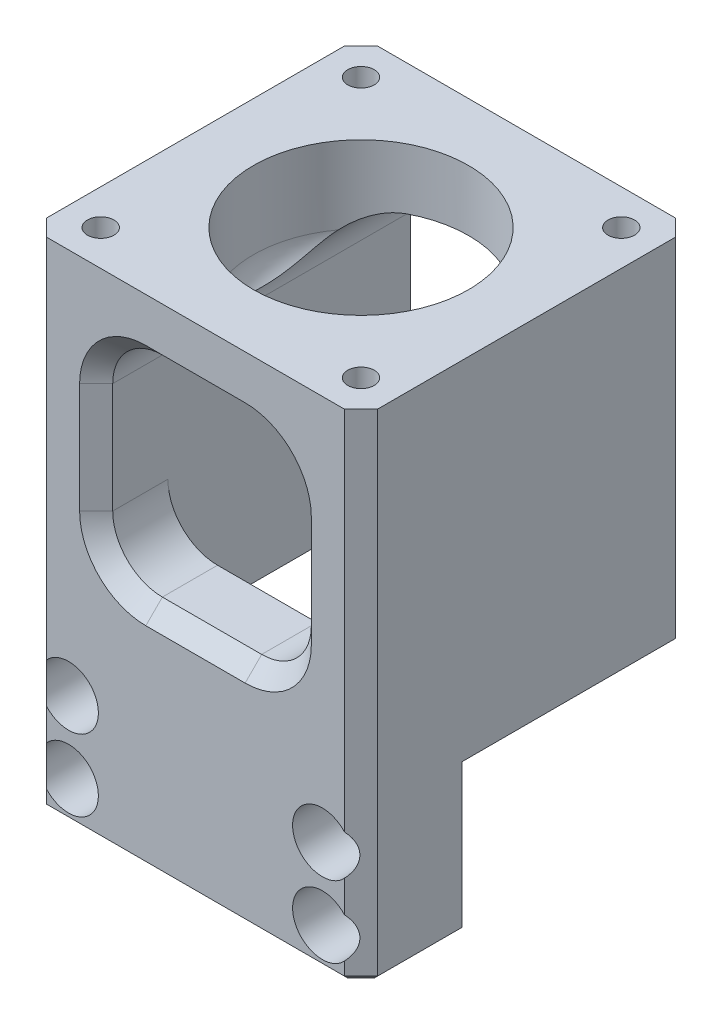
SolidWorks part; units mm, degrees
ref_plane "Front Plane" through (0, 0, 0) normal (0, 0, 1) x (1, 0, 0)
ref_plane "Top Plane" through (0, 0, 0) normal (0, 1, 0) x (1, 0, 0)
ref_plane "Right Plane" through (0, 0, 0) normal (1, 0, 0) x (0, 0, -1)
sketch "Sketch1" plane through (0, 0, 0) normal (0, 1, 0) x (1, 0, 0)
  line L1 (30, -30) -> (-30, -30)
  line L2 (30, -30) -> (30, 30)
  line L3 (30, 30) -> (-30, 30)
  line L4 (-30, -30) -> (-30, 30)
  line L5 (30, -30) -> (-30, 30) construction
  line L6 (30, 30) -> (-30, -30) construction
  point P0 (0, 0)
  dimension "D1" = 60
extrude "Boss-Extrude1" add sketch "Sketch1" along normal blind 90
sketch "Sketch2" plane through (0, 0, 0) normal (1, 0, 0) x (0, 0, -1)
  line L1 (30, 0) -> (-10.7, 0)
  line L2 (30, 0) -> (30, 26)
  line L3 (30, 26) -> (-10.7, 26)
  line L4 (-10.7, 0) -> (-10.7, 26)
  line L6 (-30, 90) -> (-30, 0) construction
  dimension "D1" = 19.3
  dimension "D2" = 26
extrude "Cut-Extrude1" cut sketch "Sketch2" against normal through all both and the other way through all
sketch "Sketch4" plane through (0, 0, -30) normal (0, 0, -1) x (-1, 0, 0)
  line L4 (0, 60.4882) -> (0, 24.8111) construction
  line L5 (-30, 90) -> (-30, 26) construction
  line L6 (18, 41) -> (-18, 41)
  line L7 (18, 41) -> (18, 79)
  line L8 (18, 79) -> (-18, 79)
  line L9 (-18, 41) -> (-18, 79)
  line L10 (18, 41) -> (-18, 79) construction
  line L11 (18, 79) -> (-18, 41) construction
  line L12 (-30, 90) -> (30, 90) construction
  line L13 (30, 26) -> (-30, 26) construction
  point P1 (0, 60)
  dimension "D1" = 12
  dimension "D2" = 11
  dimension "D3" = 15
extrude "Cut-Extrude2" cut sketch "Sketch4" against normal through all
sketch "Sketch5" plane through (0, 0, 0) normal (0, -1, 0) x (1, 0, 0)
  line L0 (-30, -30) -> (-30, 10.7) construction
  line L1 (18, -17) -> (-18, -17)
  line L2 (18, -17) -> (18, 17)
  line L3 (18, 17) -> (-18, 17)
  line L4 (-18, -17) -> (-18, 17)
  line L5 (18, -17) -> (-18, 17) construction
  line L6 (18, 17) -> (-18, -17) construction
  line L7 (-30, 30) -> (30, 30) construction
  point P0 (0, 0)
  dimension "D1" = 12
  dimension "D2" = 13
extrude "Cut-Extrude3" cut sketch "Sketch5" against normal up to surface (79 mm away) up to face at (0, 79, 0)
sketch "Sketch6" plane through (0, 90, 0) normal (0, 1, 0) x (1, 0, 0)
  circle A0 centre (0, 0) radius 19.5
  dimension "D1" = 39
extrude "Cut-Extrude4" cut sketch "Sketch6" against normal blind 20
fillet "Fillet2" radius 6 2 edges at (-19.5, 70, 0) (19.5, 70, 0)
fillet "Fillet3" radius 9 6 edges at (18, 79, 18.75) (18, 41, 23.5) (18, 41, -23.5) (-18, 41, -23.5) (-18, 41, 23.5) (-18, 79, -18.75)
chamfer "Chamfer1" distance 3 angle 45 4 edges at (-30, 58, -30) (30, 58, -30) (-30, 45, 30) (30, 45, 30)
sketch "Sketch7" plane through (0, 0, 10.7) normal (0, 0, -1) x (-1, 0, 0)
  line L0 (0, 13.5) -> (0, 0) construction
  line L1 (23, 20) -> (-23, 20) construction
  line L2 (23, 20) -> (23, 7) construction
  line L3 (23, 7) -> (-23, 7) construction
  line L4 (-23, 20) -> (-23, 7) construction
  line L5 (23, 20) -> (-23, 7) construction
  line L6 (23, 7) -> (-23, 20) construction
  line L7 (-30, 26) -> (-30, 0) construction
  line L8 (27, 26) -> (-27, 26) construction
  line L9 (-18, 0) -> (18, 0) construction
  circle A0 centre (-23, 20) radius 3.05
  circle A1 centre (-23, 7) radius 3.05
  circle A2 centre (23, 20) radius 3.05
  circle A3 centre (23, 7) radius 3.05
  point P0 (0, 13.5)
  dimension "D1" = 6.1
  dimension "D2" = 7
  dimension "D3" = 6
  dimension "D4" = 7
extrude "Cut-Extrude5" cut sketch "Sketch7" against normal through all
sketch "Sketch8" plane through (0, 0, 30) normal (0, 0, 1) x (1, 0, 0)
  circle A0 centre (-23, 20) radius 5.4
  circle A1 centre (23, 20) radius 5.4
  circle A2 centre (23, 7) radius 5.4
  circle A3 centre (-23, 7) radius 5.4
  dimension "D1" = 10.8
extrude "Cut-Extrude6" cut sketch "Sketch8" against normal blind 9.5
chamfer "Chamfer2" distance 1 angle 45 17 edges at (-30, 13, 10.7) (-30, 26, -8.15) (-28.5, 26, -28.5) (0, 26, -30) (28.5, 26, -28.5) (30, 26, -8.15) (30, 13, 10.7) (-30, 0, 18.85) (-28.5, 0, 28.5) (30, 0, 18.85) (28.5, 0, 28.5) (0, 0, 30) (-24, 0, 10.7) (24, 0, 10.7) (18, 0, 13.85) (0, 0, 17) (-18, 0, 13.85)
sketch "Sketch10" plane through (0, 90, 0) normal (0, 1, 0) x (1, 0, 0)
  line L1 (23.59, -23.59) -> (-23.59, -23.59) construction
  line L2 (23.59, -23.59) -> (23.59, 23.59) construction
  line L3 (23.59, 23.59) -> (-23.59, 23.59) construction
  line L4 (-23.59, -23.59) -> (-23.59, 23.59) construction
  line L5 (23.59, -23.59) -> (-23.59, 23.59) construction
  line L6 (23.59, 23.59) -> (-23.59, -23.59) construction
  circle A0 centre (-23.59, 23.59) radius 2.4
  circle A1 centre (23.59, 23.59) radius 2.4
  circle A2 centre (23.59, -23.59) radius 2.4
  circle A3 centre (-23.59, -23.59) radius 2.4
  point P0 (0, 0)
  dimension "D2" = 4.8
  dimension "D1" = 47.18
extrude "Cut-Extrude7" cut sketch "Sketch10" against normal blind 23
chamfer "Chamfer3" distance 3 angle 45 16 edges at (-18, 60, -30) (-15.364, 76.364, -30) (-15.364, 43.636, -30) (0, 79, -30) (0, 41, -30) (15.364, 76.364, -30) (15.364, 43.636, -30) (18, 60, -30) (-18, 60, 30) (-15.364, 76.364, 30) (-15.364, 43.636, 30) (0, 79, 30) (0, 41, 30) (15.364, 76.364, 30) (15.364, 43.636, 30) (18, 60, 30)
sketch "Sketch11" plane through (0, 0, 0) normal (0, -1, 0) x (1, 0, 0)
  line L0 (0, 0) -> (0, 22.24) construction
  circle A0 centre (0, 22.24) radius 4
  dimension "D2" = 8
  dimension "D1" = 22.24
extrude "Cut-Extrude8" cut sketch "Sketch11" against normal blind 40
sketch "Sketch12" plane through (0, 0, 0) normal (0, -1, 0) x (1, 0, 0)
  line L0 (-12, 22.24) -> (12, 22.24) construction
  circle A0 centre (-12, 22.24) radius 2
  circle A1 centre (12, 22.24) radius 2
  point P2 (0, 22.24)
  dimension "D2" = 4
  dimension "D1" = 24
extrude "Cut-Extrude9" cut sketch "Sketch12" against normal blind 11
